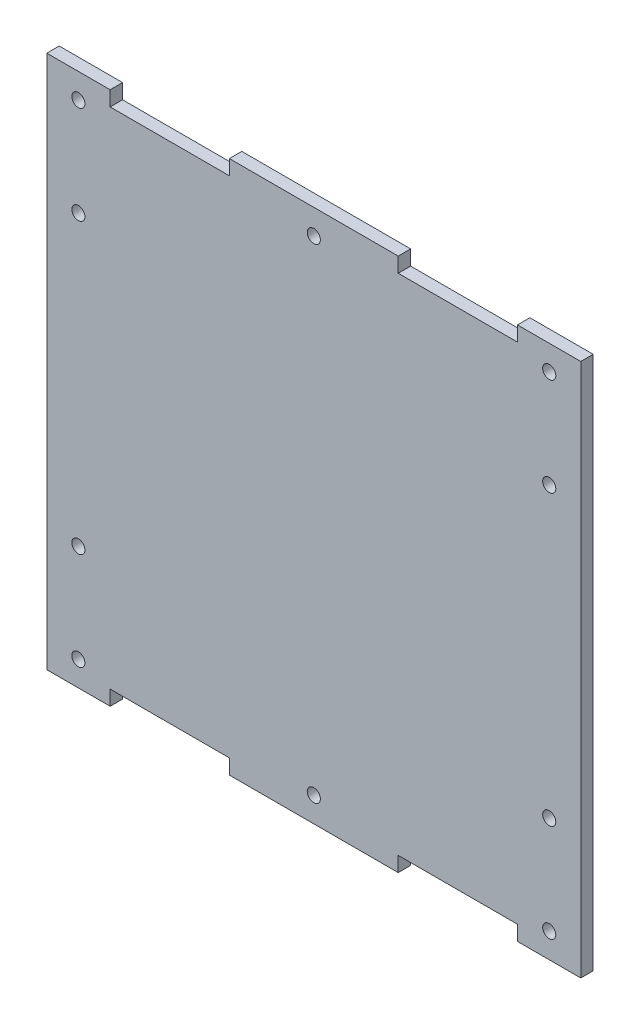
SolidWorks part; units mm, degrees
material "ABS PC"
ref_plane "Front Plane" through (0, 0, 0) normal (0, 0, 1) x (1, 0, 0)
ref_plane "Top Plane" through (0, 0, 0) normal (0, 1, 0) x (1, 0, 0)
ref_plane "Right Plane" through (0, 0, 0) normal (1, 0, 0) x (0, 0, -1)
sketch "Sketch2" plane through (0, 0, 0) normal (0, 0, 1) x (1, 0, 0)
  line L0 (-148.1492, 0) -> (167.2874, 0) construction
  line L1 (-136.525, -136.525) -> (136.525, -136.525)
  line L2 (-136.525, -136.525) -> (-136.525, 136.525)
  line L3 (-136.525, 136.525) -> (136.525, 136.525)
  line L4 (136.525, -136.525) -> (136.525, 136.525)
  line L5 (-136.525, -136.525) -> (136.525, 136.525) construction
  line L6 (-136.525, 136.525) -> (136.525, -136.525) construction
  line L7 (0, 204.6077) -> (0, -224.7364) construction
  circle A0 centre (-120.396, 123.825) radius 3.35
  circle A1 centre (-120.396, 73.787) radius 3.35
  circle A2 centre (0, 123.825) radius 3.35
  circle A3 centre (120.396, 73.787) radius 3.35
  circle A4 centre (120.396, 123.825) radius 3.35
  circle A5 centre (120.396, -123.825) radius 3.35
  circle A6 centre (120.396, -73.787) radius 3.35
  circle A7 centre (0, -123.825) radius 3.35
  circle A8 centre (-120.396, -73.787) radius 3.35
  circle A9 centre (-120.396, -123.825) radius 3.35
  point P0 (0, 0)
  dimension "D4" = 6.7
  dimension "D7" = 6.7
  dimension "D8" = 6.7
  dimension "D1" = 273.05
  dimension "D2" = 273.05
  dimension "D3" = 120.396
  dimension "D5" = 123.825
  dimension "D6" = 50.038
extrude "Boss-Extrude1" add sketch "Sketch2" along normal blind 6.35
sketch "Sketch3" plane through (0, 0, 6.35) normal (0, 0, 1) x (1, 0, 0)
  line L0 (0, 160.7885) -> (0, -171.3941) construction
  line L1 (-158.7053, 0) -> (205.6729, 0) construction
  line L4 (136.525, 136.525) -> (-136.525, 136.525) construction
  line L5 (104.14, 128.905) -> (43.18, 128.905)
  line L6 (104.14, 146.1851) -> (43.18, 146.1851)
  line L7 (-104.14, 146.1851) -> (-104.14, 128.905)
  line L8 (43.18, 128.905) -> (43.18, 146.1851)
  line L9 (104.14, 146.1851) -> (104.14, 128.905)
  line L10 (-104.14, -128.905) -> (-43.18, -128.905)
  line L11 (-43.18, 128.905) -> (-43.18, 146.1851)
  line L12 (-104.14, -146.1851) -> (-43.18, -146.1851)
  line L13 (-104.14, 146.1851) -> (-43.18, 146.1851)
  line L14 (-104.14, 128.905) -> (-43.18, 128.905)
  line L15 (-43.18, -128.905) -> (-43.18, -146.1851)
  line L16 (104.14, -146.1851) -> (104.14, -128.905)
  line L17 (43.18, -128.905) -> (43.18, -146.1851)
  line L18 (-104.14, -146.1851) -> (-104.14, -128.905)
  line L19 (104.14, -146.1851) -> (43.18, -146.1851)
  line L20 (104.14, -128.905) -> (43.18, -128.905)
  dimension "D1" = 7.62
  dimension "D2" = 43.18
  dimension "D3" = 104.14
extrude "Cut-Extrude1" cut sketch "Sketch3" against normal through all
